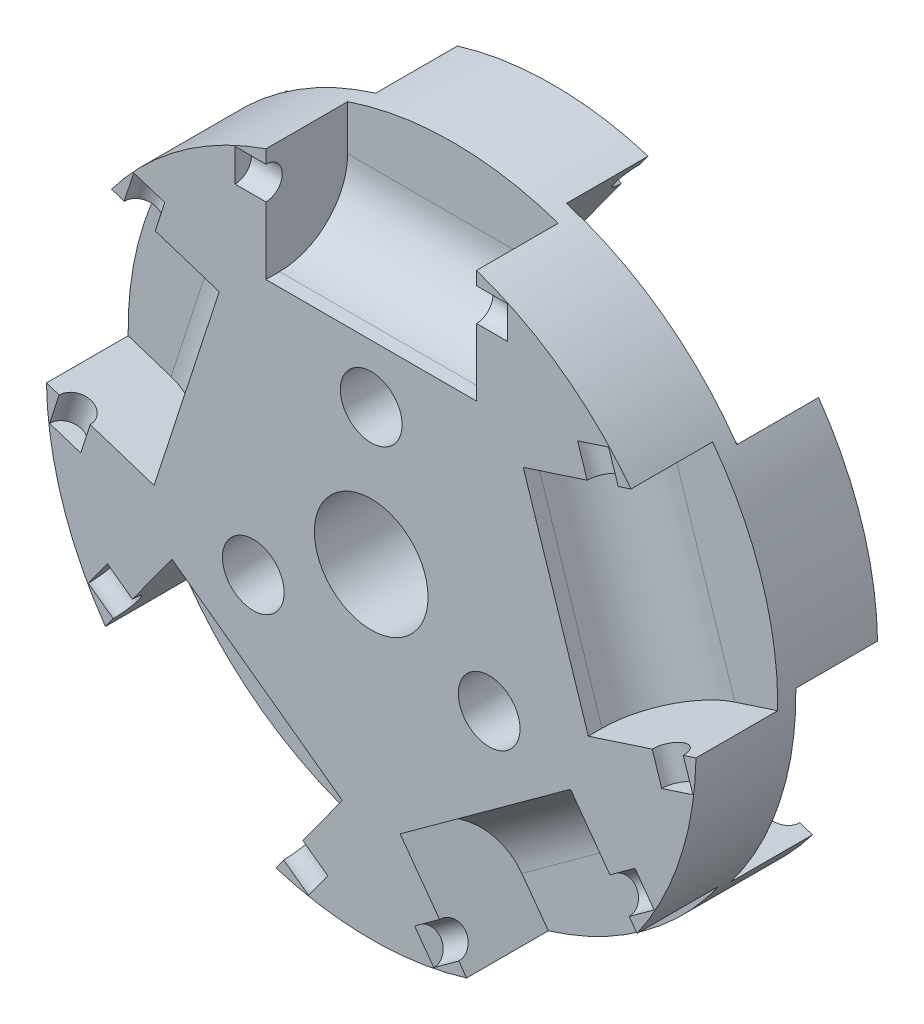
SolidWorks part; units mm, degrees
other "Markup1"
sketch "Sketch8" plane through (32.7336, 32.7336, 0) normal (0.5701, 0.1846, 0.8006) x (0.8043, 0.0736, -0.5897)
ref_plane "Front Plane" through (0, 0, 0) normal (0, 0, 1) x (1, 0, 0)
ref_plane "Top Plane" through (0, 0, 0) normal (0, 1, 0) x (1, 0, 0)
ref_plane "Right Plane" through (0, 0, 0) normal (1, 0, 0) x (0, 0, -1)
sketch "Sketch1" plane through (0, 0, 0) normal (0, 0, 1) x (1, 0, 0)
  circle A0 centre (0, 0) radius 22.7203
  dimension "D1" = 45.4406
extrude "Boss-Extrude2" add sketch "Sketch1" against normal blind 6.35
sketch "Sketch2" plane through (0, 0, 0) normal (0, 0, 1) x (1, 0, 0)
  line L1 (-12.7, 22.7203) -> (12.7, 22.7203) construction
  line L2 (-7.366, 23.9903) -> (7.366, 23.9903)
  line L3 (-7.366, 23.9903) -> (-7.366, 13.5763)
  line L4 (-7.366, 13.5763) -> (7.366, 13.5763)
  line L5 (7.366, 23.9903) -> (7.366, 13.5763)
  line L6 (-7.366, 23.9903) -> (7.366, 13.5763) construction
  line L7 (-7.366, 13.5763) -> (7.366, 23.9903) construction
  line L35 (0, 0) -> (0, 22.7203) construction
  circle A1 centre (0, 0) radius 22.7203 construction
  point P10 (0, 18.7833)
  circle M7 centre (0, 0) radius 22.7203
  dimension "D1" = 14.732
  dimension "D2" = 10.414
  dimension "D3" = 1.27
  dimension "D4" = 25.4
extrude "Cut-Extrude2" cut sketch "Sketch2" against normal blind 5.715 contours L5 L3 L4 M7 | L3 L2 L5 L4 region at (0, 17.9536, 0)
pattern_circular "CirPattern1" count 5 over 360 about axis through (0, 0, 0) along (0, 0, 1) of "Cut-Extrude2"
ref_plane "Plane1" through (0, 0, 0) normal (1, 0, 0) x (0, 0, -1)
sketch "Sketch4" plane through (0, 0, 0) normal (1, 0, 0) x (0, 0, -1)
  line L0 (5.715, 13.5763) -> (0, 13.5763) construction
  circle A0 centre (0, 19.4183) radius 1.143
  dimension "D1" = 2.286
  dimension "D2" = 5.842
extrude "Cut-Extrude4" cut sketch "Sketch4" against normal mid plane 19.05
pattern_circular "CirPattern2" count 5 over 360 about axis through (0, 0, 0) along (0, 0, 1) of "Cut-Extrude4"
sketch "Sketch5" plane through (0, 0, 0) normal (0, 0, 1) x (1, 0, 0)
  circle A0 centre (0, 0) radius 3.9751
  dimension "D1" = 7.9502
extrude "Cut-Extrude5" cut sketch "Sketch5" against normal through all
sketch "Sketch6" plane through (0, 0, -6.35) normal (0, 0, -1) x (-1, 0, 0)
  circle A4 centre (0, 9.525) radius 2.159
  circle A5 centre (8.2489, -4.7625) radius 2.159
  circle A6 centre (-8.2489, -4.7625) radius 2.159
  point P2 (-11.6871, -5.1063)
  point P3 (0, 0)
  point P9 (0, 0)
  dimension "D1" = 4.318
  dimension "D2" = 9.525
extrude "Cut-Extrude7" cut sketch "Sketch6" against normal through all
sketch "Sketch9" plane through (0, 0, -6.35) normal (0, 0, -1) x (-1, 0, 0)
  circle A0 centre (0, 0) radius 22.7203
  circle A5 centre (-8.2489, -4.7625) radius 2.159 construction
  circle A6 centre (8.2489, -4.7625) radius 2.159 construction
  circle A7 centre (0, 9.525) radius 2.159 construction
  circle A8 centre (-8.2489, -4.7625) radius 2.159
  circle A9 centre (0, 0) radius 22.7203 construction
  circle A10 centre (8.2489, -4.7625) radius 2.159
  circle A11 centre (0, 9.525) radius 2.159
  circle A12 centre (0, 0) radius 3.9751 construction
  circle A13 centre (0, 0) radius 3.9751
extrude "Boss-Extrude3" add sketch "Sketch9" along normal blind 6.35
sketch "Sketch10" plane through (0, 0, -12.7) normal (0, 0, -1) x (-1, 0, 0)
  line L0 (-26.0547, 18.3811) -> (-0.6547, 18.3811) construction
  line L1 (-2.0207, 15.3131) -> (-13.9392, 6.6538)
  line L2 (-2.0207, 15.3131) -> (-8.1419, 23.7382)
  line L3 (-8.1419, 23.7382) -> (-20.0604, 15.0789)
  line L4 (-13.9392, 6.6538) -> (-20.0604, 15.0789)
  line L5 (-2.0207, 15.3131) -> (-20.0604, 15.0789) construction
  line L6 (-8.1419, 23.7382) -> (-13.9392, 6.6538) construction
  line L7 (0, 0) -> (-13.3547, 18.3811) construction
  line L8 (0, 0) -> (0, 40.3277) construction
  circle A2 centre (0, 0) radius 22.7203 construction
  point P8 (-11.0405, 15.196)
  dimension "D1" = 1.27
  dimension "D2" = 14.732
  dimension "D3" = 10.414
  dimension "D4" = 25.4
  dimension "D5" = 36
extrude "Cut-Extrude8" cut sketch "Sketch10" against normal blind 5.715
pattern_circular "CirPattern3" count 5 over 360 about axis through (0, 0, -12.7) along (0, 0, -1) of "Cut-Extrude8"
ref_plane "Plane2" through (0, 0, 0) normal (-0.809, 0.5878, 0) x (0, 0, -1)
sketch "Sketch11" plane through (0, 0, 0) normal (-0.809, 0.5878, 0) x (0, 0, -1)
  line L5 (6.985, -13.5763) -> (12.7, -13.5763) construction
  line L6 (12.7, -21.4931) -> (12.7, -13.6472) construction
  circle A0 centre (12.7, -19.4183) radius 1.143
  dimension "D1" = 2.286
  dimension "D2" = 5.842
extrude "Cut-Extrude9" cut sketch "Sketch11" against normal mid plane 19.05
pattern_circular "CirPattern4" count 5 over 360 about axis through (0, 0, -12.7) along (0, 0, -1) of "Cut-Extrude9"
fillet "Fillet1" radius 4.7625 10 edges at (12.9118, -4.1953, -6.985) (0, -13.5763, -6.985) (-12.9118, -4.1953, -6.985) (7.9799, 10.9835, -6.985) (-7.9799, 10.9835, -6.985) (-7.9799, -10.9835, -5.715) (7.9799, -10.9835, -5.715) (12.9118, 4.1953, -5.715) (0, 13.5763, -5.715) (-12.9118, 4.1953, -5.715)
